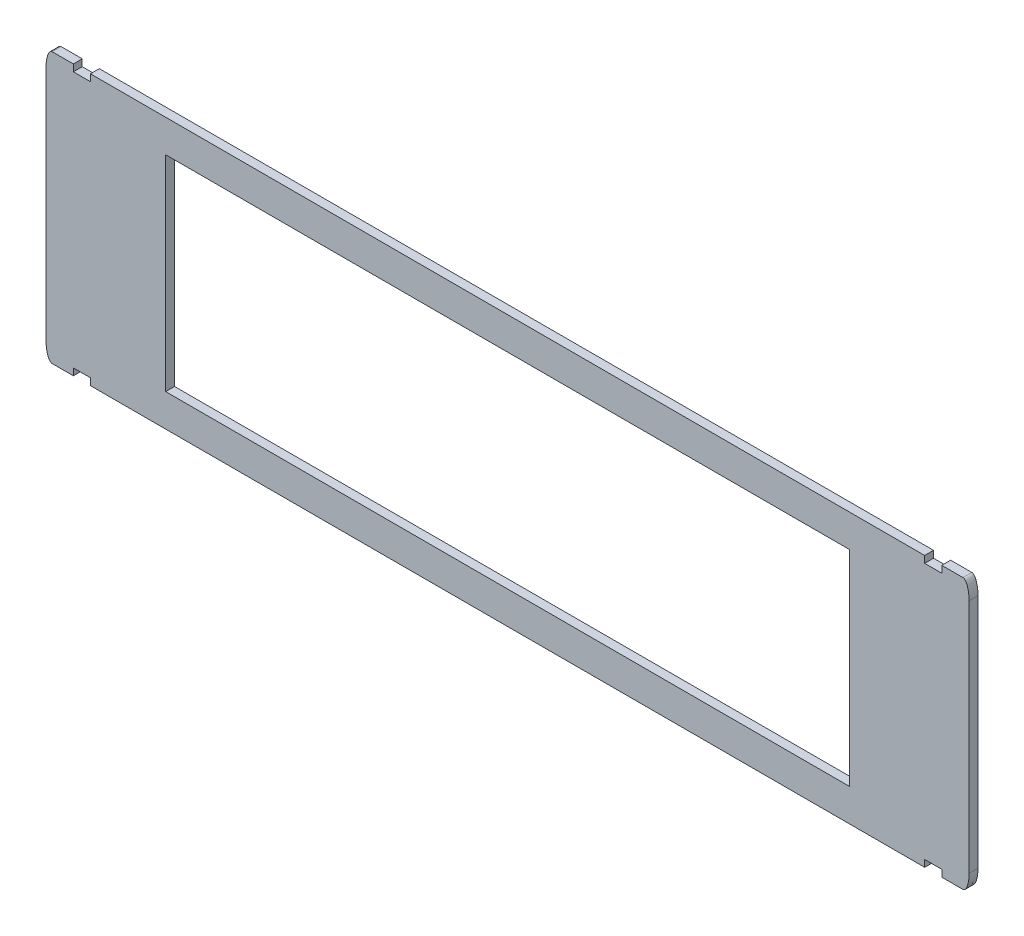
SolidWorks part; units mm, degrees
ref_plane "前视基准面" through (0, 0, 0) normal (0, 0, 1) x (1, 0, 0)
ref_plane "上视基准面" through (0, 0, 0) normal (0, 1, 0) x (1, 0, 0)
ref_plane "右视基准面" through (0, 0, 0) normal (1, 0, 0) x (0, 0, -1)
sketch "草图1" plane through (0, 0, 0) normal (0, 0, 1) x (1, 0, 0)
  line L1 (-135, 39.5) -> (135, 39.5)
  line L2 (-135, 39.5) -> (-135, -39.5)
  line L3 (-135, -39.5) -> (135, -39.5)
  line L4 (135, 39.5) -> (135, -39.5)
  line L5 (-135, 39.5) -> (135, -39.5) construction
  line L6 (-135, -39.5) -> (135, 39.5) construction
  point P0 (0, 0)
  dimension "D1" = 79
  dimension "D2" = 270
extrude "凸台-拉伸1" add sketch "草图1" along normal blind 2.6
sketch "草图2" plane through (0, 0, 2.6) normal (0, 0, 1) x (1, 0, 0)
  line L1 (-100, 30) -> (100, 30)
  line L2 (-100, 30) -> (-100, -30)
  line L3 (-100, -30) -> (100, -30)
  line L4 (100, 30) -> (100, -30)
  line L5 (-100, 30) -> (100, -30) construction
  line L6 (-100, -30) -> (100, 30) construction
  point P0 (0, 0)
  dimension "D1" = 200
  dimension "D2" = 60
extrude "切除-拉伸1" cut sketch "草图2" against normal through all
fillet "圆角1" radius 1.8 4 edges at (135, -39.5, 1.3) (135, 39.5, 1.3) (-135, -39.5, 1.3) (-135, 39.5, 1.3) second distance 5 first distance on face at (0, -39.5, 1.3) first distance on face at (0, 39.5, 1.3)
sketch "草图3" plane through (0, 0, 2.6) normal (0, 0, 1) x (1, 0, 0)
  line L0 (133.2, 39.5) -> (-133.2, 39.5) construction
  line L1 (-127, 39.5) -> (-122, 39.5)
  line L2 (-127, 39.5) -> (-127, 37.5)
  line L3 (-127, 37.5) -> (-122, 37.5)
  line L4 (-122, 39.5) -> (-122, 37.5)
  line L5 (-135, 34.5) -> (-135, -34.5) construction
  point P6 (-127, 38.5)
  dimension "D1" = 2
  dimension "D2" = 5
  dimension "D3" = 8
extrude "切除-拉伸2" cut sketch "草图3" against normal through all
mirror "镜向1" about plane through (0, 0, 0) normal (0, 1, 0) of "切除-拉伸2"
mirror "镜向2" about plane through (0, 0, 0) normal (1, 0, 0) of "切除-拉伸2", "镜向1"
